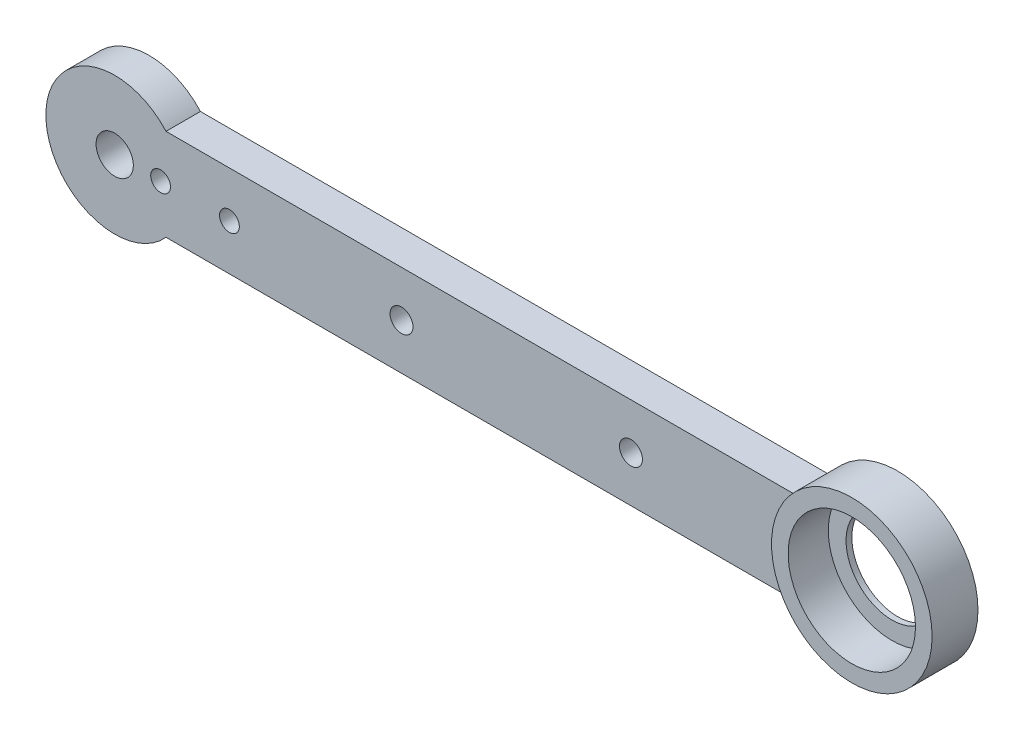
SolidWorks part; units mm, degrees
ref_plane "Front Plane" through (0, 0, 0) normal (0, 0, 1) x (1, 0, 0)
ref_plane "Top Plane" through (0, 0, 0) normal (0, 1, 0) x (1, 0, 0)
ref_plane "Right Plane" through (0, 0, 0) normal (1, 0, 0) x (0, 0, -1)
sketch "Sketch1" plane through (0, 0, 0) normal (0, 0, 1) x (1, 0, 0)
  line L0 (0, -8) -> (130, -8)
  line L1 (130, -8) -> (130, 8)
  line L2 (130, 8) -> (0, 8)
  line L3 (0, 8) -> (0, -8)
extrude "Boss-Extrude1" add sketch "Sketch1" along normal blind 6 from offset 3
sketch "Sketch2" plane through (0, 0, 0) normal (0, 0, 1) x (1, 0, 0)
  circle A0 centre (0, 0) radius 12
extrude "Boss-Extrude2" add sketch "Sketch2" along normal blind 6 from offset 3
sketch "Sketch3" plane through (0, 0, 0) normal (0, 0, 1) x (1, 0, 0)
  circle A0 centre (130, 0) radius 14
extrude "Boss-Extrude3" add sketch "Sketch3" along normal blind 6 from offset 3
sketch "Sketch4" plane through (0, 0, 0) normal (0, 0, 1) x (1, 0, 0)
  circle A0 centre (130, 0) radius 14
extrude "Boss-Extrude4" add sketch "Sketch4" along normal blind 8 from offset 2.5
sketch "Sketch5" plane through (0, 0, 0) normal (0, 0, 1) x (1, 0, 0)
  circle A0 centre (0, 0) radius 3.25
extrude "Cut-Extrude1" cut sketch "Sketch5" against normal through all and the other way through all
sketch "Sketch6" plane through (0, 0, 0) normal (0, 0, 1) x (1, 0, 0)
  circle A0 centre (8, 0) radius 1.725
  circle A1 centre (20, 0) radius 1.725
extrude "Cut-Extrude2" cut sketch "Sketch6" against normal through all and the other way through all
sketch "Sketch7" plane through (0, 0, 0) normal (0, 0, 1) x (1, 0, 0)
  circle A0 centre (8, 0) radius 2.9
extrude "Cut-Extrude3" cut sketch "Sketch7" along normal blind 2.2 from offset 3
sketch "Sketch8" plane through (0, 0, 0) normal (0, 0, 1) x (1, 0, 0)
  circle A0 centre (20, 0) radius 2.9
extrude "Cut-Extrude4" cut sketch "Sketch8" along normal blind 2.2 from offset 3
sketch "Sketch9" plane through (0, 0, 0) normal (0, 0, 1) x (1, 0, 0)
  circle A0 centre (130, 0) radius 11.1
extrude "Cut-Extrude5" cut sketch "Sketch9" along normal blind 7 from offset 3.5
sketch "Sketch10" plane through (0, 0, 0) normal (0, 0, 1) x (1, 0, 0)
  circle A0 centre (130, 0) radius 8
extrude "Cut-Extrude6" cut sketch "Sketch10" against normal through all and the other way through all
sketch "Sketch11" plane through (0, 0, 0) normal (0, 0, 1) x (1, 0, 0)
  circle A0 centre (50, 0) radius 2
  circle A1 centre (90, 0) radius 2
extrude "Cut-Extrude7" cut sketch "Sketch11" along normal blind 4 from offset 5
